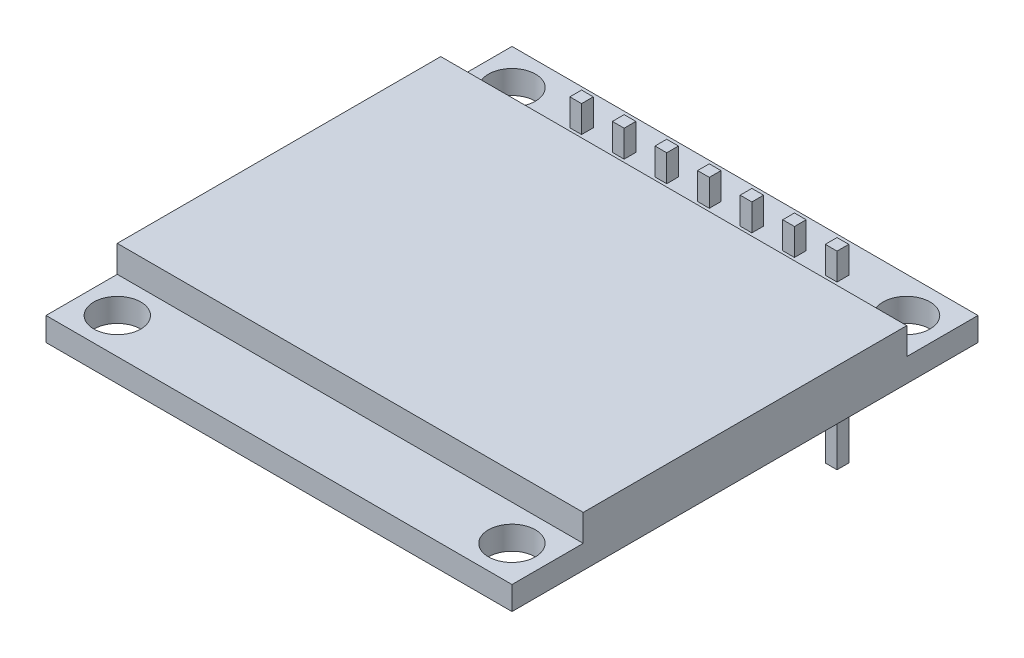
SolidWorks part; units mm, degrees
ref_plane "前视基准面" through (0, 0, 0) normal (0, 0, 1) x (1, 0, 0)
ref_plane "上视基准面" through (0, 0, 0) normal (0, 1, 0) x (1, 0, 0)
ref_plane "右视基准面" through (0, 0, 0) normal (1, 0, 0) x (0, 0, -1)
other "Configuration Table"
sketch "草图1" plane through (0, 0, 0) normal (0, 1, 0) x (1, 0, 0)
  line L0 (13.9, -23.55) -> (13.9, -27.8)
  line L1 (0, 0) -> (27.8, 0)
  line L2 (0, 0) -> (0, -27.8)
  line L3 (0, -27.8) -> (27.8, -27.8)
  line L4 (27.8, 0) -> (27.8, -27.8)
  line L9 (0, -4.25) -> (27.8, -4.25)
  line L10 (0, -4.25) -> (0, -23.55)
  line L11 (0, -23.55) -> (27.8, -23.55)
  line L12 (27.8, -4.25) -> (27.8, -23.55)
  line L13 (7.55, -0.86) -> (10.09, -0.86)
  line L18 (5.01, -0.86) -> (7.55, -0.86)
  line L19 (5.01, -0.86) -> (5.01, -3.4)
  line L20 (5.01, -3.4) -> (7.55, -3.4)
  line L21 (7.55, -0.86) -> (7.55, -3.4)
  line L22 (5.01, -0.86) -> (7.55, -3.4) construction
  line L23 (5.01, -3.4) -> (7.55, -0.86) construction
  line L24 (5.93, -2.48) -> (6.63, -2.48)
  line L25 (5.93, -2.48) -> (5.93, -1.78)
  line L26 (5.93, -1.78) -> (6.63, -1.78)
  line L27 (6.63, -2.48) -> (6.63, -1.78)
  line L28 (5.93, -2.48) -> (6.63, -1.78) construction
  line L29 (5.93, -1.78) -> (6.63, -2.48) construction
  line L30 (7.55, -0.86) -> (7.55, -3.4)
  line L31 (7.55, -3.4) -> (10.09, -3.4)
  line L32 (10.09, -0.86) -> (10.09, -3.4)
  line L33 (8.47, -2.48) -> (9.17, -2.48)
  line L34 (8.47, -2.48) -> (8.47, -1.78)
  line L35 (8.47, -1.78) -> (9.17, -1.78)
  line L36 (9.17, -2.48) -> (9.17, -1.78)
  line L37 (7.55, -0.86) -> (10.09, -3.4) construction
  line L38 (7.55, -3.4) -> (10.09, -0.86) construction
  line L39 (8.47, -2.48) -> (9.17, -1.78) construction
  line L40 (8.47, -1.78) -> (9.17, -2.48) construction
  line L41 (10.09, -0.86) -> (12.63, -0.86)
  line L42 (10.09, -0.86) -> (10.09, -3.4)
  line L43 (10.09, -3.4) -> (12.63, -3.4)
  line L44 (12.63, -0.86) -> (12.63, -3.4)
  line L45 (11.01, -2.48) -> (11.71, -2.48)
  line L46 (11.01, -2.48) -> (11.01, -1.78)
  line L47 (11.01, -1.78) -> (11.71, -1.78)
  line L48 (11.71, -2.48) -> (11.71, -1.78)
  line L49 (10.09, -0.86) -> (12.63, -3.4) construction
  line L50 (10.09, -3.4) -> (12.63, -0.86) construction
  line L51 (11.01, -2.48) -> (11.71, -1.78) construction
  line L52 (11.01, -1.78) -> (11.71, -2.48) construction
  line L53 (12.63, -0.86) -> (15.17, -0.86)
  line L54 (12.63, -0.86) -> (12.63, -3.4)
  line L55 (12.63, -3.4) -> (15.17, -3.4)
  line L56 (15.17, -0.86) -> (15.17, -3.4)
  line L57 (13.55, -2.48) -> (14.25, -2.48)
  line L58 (13.55, -2.48) -> (13.55, -1.78)
  line L59 (13.55, -1.78) -> (14.25, -1.78)
  line L60 (14.25, -2.48) -> (14.25, -1.78)
  line L61 (12.63, -0.86) -> (15.17, -3.4) construction
  line L62 (12.63, -3.4) -> (15.17, -0.86) construction
  line L63 (13.55, -2.48) -> (14.25, -1.78) construction
  line L64 (13.55, -1.78) -> (14.25, -2.48) construction
  line L65 (15.17, -0.86) -> (17.71, -0.86)
  line L66 (15.17, -0.86) -> (15.17, -3.4)
  line L67 (15.17, -3.4) -> (17.71, -3.4)
  line L68 (17.71, -0.86) -> (17.71, -3.4)
  line L69 (16.09, -2.48) -> (16.79, -2.48)
  line L70 (16.09, -2.48) -> (16.09, -1.78)
  line L71 (16.09, -1.78) -> (16.79, -1.78)
  line L72 (16.79, -2.48) -> (16.79, -1.78)
  line L73 (15.17, -0.86) -> (17.71, -3.4) construction
  line L74 (15.17, -3.4) -> (17.71, -0.86) construction
  line L75 (16.09, -2.48) -> (16.79, -1.78) construction
  line L76 (16.09, -1.78) -> (16.79, -2.48) construction
  line L77 (17.71, -0.86) -> (20.25, -0.86)
  line L78 (17.71, -0.86) -> (17.71, -3.4)
  line L79 (17.71, -3.4) -> (20.25, -3.4)
  line L80 (20.25, -0.86) -> (20.25, -3.4)
  line L81 (18.63, -2.48) -> (19.33, -2.48)
  line L82 (18.63, -2.48) -> (18.63, -1.78)
  line L83 (18.63, -1.78) -> (19.33, -1.78)
  line L84 (19.33, -2.48) -> (19.33, -1.78)
  line L85 (17.71, -0.86) -> (20.25, -3.4) construction
  line L86 (17.71, -3.4) -> (20.25, -0.86) construction
  line L87 (18.63, -2.48) -> (19.33, -1.78) construction
  line L88 (18.63, -1.78) -> (19.33, -2.48) construction
  line L89 (20.25, -0.86) -> (22.79, -0.86)
  line L90 (20.25, -0.86) -> (20.25, -3.4)
  line L91 (20.25, -3.4) -> (22.79, -3.4)
  line L92 (22.79, -0.86) -> (22.79, -3.4)
  line L93 (21.17, -2.48) -> (21.87, -2.48)
  line L94 (21.17, -2.48) -> (21.17, -1.78)
  line L95 (21.17, -1.78) -> (21.87, -1.78)
  line L96 (21.87, -2.48) -> (21.87, -1.78)
  line L97 (20.25, -0.86) -> (22.79, -3.4) construction
  line L98 (20.25, -3.4) -> (22.79, -0.86) construction
  line L99 (21.17, -2.48) -> (21.87, -1.78) construction
  line L100 (21.17, -1.78) -> (21.87, -2.48) construction
  circle A0 centre (2.13, -2.13) radius 1.4
  circle A1 centre (25.67, -2.13) radius 1.4
  circle A2 centre (2.13, -25.675) radius 1.4
  circle A3 centre (25.67, -25.675) radius 1.4
  point P9 (0, -13.9)
  point P10 (0, -13.9)
  point P19 (13.9, -25.675)
  point P20 (6.28, -2.13)
  point P25 (6.28, -2.13)
  point P32 (0, 0)
  point P33 (8.82, -2.13)
  point P38 (8.82, -2.13)
  point P43 (11.36, -2.13)
  point P48 (11.36, -2.13)
  point P53 (13.9, -2.13)
  point P58 (13.9, -2.13)
  point P63 (16.44, -2.13)
  point P68 (16.44, -2.13)
  point P73 (18.98, -2.13)
  point P78 (18.98, -2.13)
  point P83 (21.52, -2.13)
  point P88 (21.52, -2.13)
  dimension "D3" = 2.8
  dimension "D9" = 0.7
  dimension "D1" = 27.8
  dimension "D2" = 19.3
  dimension "D4" = 2.125
  dimension "D5" = 2.13
  dimension "D6" = 2.13
  dimension "D7" = 2.13
  dimension "D8" = 2.54
  dimension "D10" = 7
extrude "凸台-拉伸1" add sketch "草图1" along normal blind 1.4 contours L3 L4 L1 L2 | A0 | A1 | A2 | A3
extrude "凸台-拉伸2" add sketch "草图1<3>" along normal blind 3 contours L9 L12 L11 L10
sketch "草图1<3>" plane through (0, 0, 0) normal (0, 1, 0) x (1, 0, 0) same geometry as "草图1"
extrude "凸台-拉伸3" add sketch "草图1<4>" against normal blind 2.54 contours L89 L92 L91 L90 | L77 L80 L79 L78 | L65 L68 L67 L66 | L53 L56 L55 L54 | L41 L44 L43 L42 | L13 L32 L31 L30 | L18 L21 L20 L19
sketch "草图1<4>" plane through (0, 0, 0) normal (0, 1, 0) x (1, 0, 0) same geometry as "草图1"
extrude "凸台-拉伸4" add sketch "草图1<5>" against normal blind 11.3 from surface contours L95 L96 L93 L94 | L83 L84 L81 L82 | L71 L72 L69 L70 | L59 L60 L57 L58 | L47 L48 L45 L46 | L35 L36 L33 L34 | L26 L27 L24 L25 starting at face at (13.9, 3, 13.9)
sketch "草图1<5>" plane through (0, 0, 0) normal (0, 1, 0) x (1, 0, 0) same geometry as "草图1"
